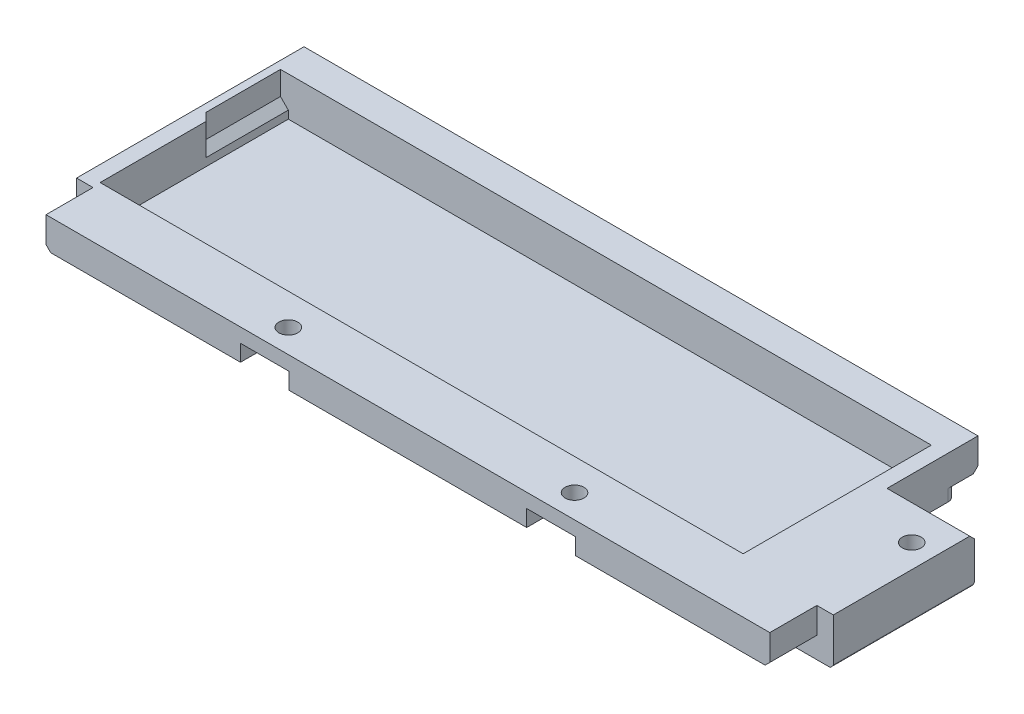
SolidWorks part; units mm, degrees
ref_plane "前视基准面" through (0, 0, 0) normal (0, 0, 1) x (1, 0, 0)
ref_plane "上视基准面" through (0, 0, 0) normal (0, 1, 0) x (1, 0, 0)
ref_plane "右视基准面" through (0, 0, 0) normal (1, 0, 0) x (0, 0, -1)
sketch "草图1" plane through (0, 0, 0) normal (0, 1, 0) x (1, 0, 0)
  line L1 (0, 0) -> (96.5, 0)
  line L2 (0, 0) -> (0, 35)
  line L3 (0, 35) -> (96.5, 35)
  line L4 (96.5, 0) -> (96.5, 35)
  dimension "D1" = 35
  dimension "D2" = 96.5
extrude "凸台-拉伸1" add sketch "草图1" along normal blind 6
sketch "草图2" plane through (0, 6, 0) normal (0, 1, 0) x (1, 0, 0)
  line L0 (96.5, 35) -> (0, 35) construction
  line L1 (2, 7) -> (84, 7)
  line L2 (2, 7) -> (2, 31)
  line L3 (2, 31) -> (84, 31)
  line L4 (84, 7) -> (84, 31)
  line L5 (0, 35) -> (0, 0) construction
  dimension "D1" = 24
  dimension "D2" = 82
  dimension "D3" = 4
  dimension "D4" = 2
extrude "切除-拉伸1" cut sketch "草图2" against normal blind 5
sketch "草图3" plane through (0, 0, 0) normal (0, 0, 1) x (1, 0, 0)
  line L0 (96.5, 6) -> (96.5, 0) construction
  line L1 (0, 0) -> (96.5, 0) construction
  line L2 (0, 6) -> (0, 0) construction
  line L3 (96.5, 6) -> (96.5, 0)
  line L4 (0, 0) -> (96.5, 0)
  line L5 (0, 6) -> (0, 0)
  line L6 (94.4, 6) -> (94.4, 2.1)
  line L7 (2.1, 2.1) -> (94.4, 2.1)
  line L8 (2.1, 6) -> (2.1, 2.1)
  line L9 (0, 6) -> (2.1, 6)
  line L10 (94.4, 6) -> (96.5, 6)
  dimension "D1" = 2.1
extrude "切除-拉伸2" cut sketch "草图3" against normal blind 6
sketch "草图4" plane through (0, 0, 0) normal (0, -1, 0) x (1, 0, 0)
  line L0 (0, -32.2) -> (86, -32.2) construction
  line L1 (86, -32.2) -> (86, -25) construction
  line L2 (87, -24) -> (96.5, -24) construction
  line L3 (0, -32.2) -> (85.95, -32.2)
  line L4 (86, -32.2) -> (86, -24) construction
  line L5 (86, -24) -> (96.5, -24)
  line L6 (86, -24) -> (85.95, -24)
  line L7 (85.95, -24) -> (85.95, -32.2)
  line L10 (96.5, -6) -> (0, -6)
  line L11 (0, -6) -> (0, -35)
  line L12 (0, -35) -> (96.5, -35)
  line L13 (96.5, -35) -> (96.5, -6)
  line L15 (0, -32.2) -> (0, -35)
  line L16 (0, -35) -> (96.5, -35)
  line L17 (96.5, -35) -> (96.5, -24)
  dimension "D2" = 0.1
  dimension "D1" = 0
extrude "切除-拉伸3" cut sketch "草图4" against normal blind 2.1
fillet "圆角1" radius 1 1 edges at (85.95, 1.05, -32.2)
chamfer "倒角1" distance 0.6 angle 45 4 edges at (42.475, 0, -32.2) (85.6571, 0, -31.9071) (85.95, 0, -27.6) (91.225, 0, -24)
chamfer "倒角2" distance 0.4 angle 45 2 edges at (0, 0, -18.8) (96.5, 0, -14.7)
fillet "圆角2" radius 0.2 4 edges at (0, 0.4, -19) (0.4, 0, -18.8) (96.1, 0, -14.7) (96.5, 0.4, -14.9)
sketch "草图5" plane through (0, 2.1, 0) normal (0, -1, 0) x (1, 0, 0)
  line L0 (85.95, -24) -> (85.95, -31.2) construction
  line L1 (96.5, -35) -> (85.95, -35)
  line L2 (96.5, -35) -> (96.5, -24)
  line L3 (96.5, -24) -> (85.95, -24)
  line L4 (85.95, -35) -> (85.95, -24)
  line L5 (96.5, -24) -> (85.95, -24) construction
extrude "切除-拉伸5" cut sketch "草图5" against normal through all
chamfer "倒角3" distance 0.6 angle 45 3 edges at (2.1, 2.1, -3) (94.4, 2.1, -3) (91.225, 6, -24)
chamfer "倒角4" distance 0.6 angle 45 1 edges at (42.975, 2.1, -35)
sketch "草图6" plane through (0, 6, 0) normal (0, 1, 0) x (1, 0, 0)
  line L1 (2, 31) -> (1, 31)
  line L2 (2, 31) -> (2, 21.5)
  line L3 (2, 21.5) -> (1, 21.5)
  line L4 (1, 31) -> (1, 21.5)
  dimension "D1" = 9.5
  dimension "D2" = 1
extrude "切除-拉伸6" cut sketch "草图6" against normal blind 3
chamfer "倒角5" distance 1 angle 45 1 edges at (2, 3, -26.25)
chamfer "倒角6" distance 1 angle 45 1 edges at (2, 4, -21.5)
sketch "草图7" plane through (0, 0, 0) normal (0, 0, 1) x (1, 0, 0)
  line L0 (69.5, 2) -> (69.5, 4) construction
  line L1 (63.5, 4) -> (63.5, 2) construction
  line L2 (33, 2) -> (33, 4) construction
  line L3 (27, 4) -> (27, 2) construction
  line L4 (69.5, 2) -> (69.5, 4) construction
  line L5 (63.5, 4) -> (63.5, 2) construction
  line L6 (33, 2) -> (33, 4) construction
  line L7 (27, 4) -> (27, 2) construction
  line L8 (27, 4) -> (33, 4) construction
  line L9 (63.5, 4) -> (69.5, 4) construction
  line L10 (93.8, 2.1) -> (2.7, 2.1) construction
  line L11 (69.6, 2.1) -> (63.4, 2.1)
  line L12 (26.9, 2.1) -> (26.9, 4.2)
  line L13 (26.9, 4.2) -> (33.1, 4.2)
  line L14 (33.1, 4.2) -> (33.1, 2.1)
  line L15 (63.4, 2.1) -> (63.4, 4.2)
  line L16 (63.4, 4.2) -> (69.6, 4.2)
  line L17 (69.6, 4.2) -> (69.6, 2.1)
  line L18 (33.1, 2.1) -> (26.9, 2.1)
  dimension "D1" = 0.1
  dimension "D2" = 0.1
  dimension "D3" = 0.2
  dimension "D4" = 0.1
extrude "切除-拉伸7" cut sketch "草图7" against normal blind 6
sketch "草图8" plane through (0, 4.2, 0) normal (0, -1, 0) x (1, 0, 0)
  circle A0 centre (66.5, -3) radius 1.2 construction
  circle A1 centre (30, -3) radius 1.2 construction
  circle A2 centre (66.5, -3) radius 1.2
  circle A3 centre (30, -3) radius 1.2
extrude "切除-拉伸8" cut sketch "草图8" against normal through all
ref_plane "基准面1" through (71.649, 13.84, -6.45) normal (0, 0, 1) x (1, 0, 0)
ref_plane "基准面2" through (59.6, 9.54, -28.6) normal (0, 0, 1) x (1, 0, 0)
sketch "草图11" plane through (0, 0, 0) normal (0, -1, 0) x (1, 0, 0)
  circle A0 centre (93.5, -19) radius 1.5 construction
  circle A1 centre (93.5, -19) radius 1.5 construction
  circle A2 centre (93.5, -19) radius 1.2
  circle A3 centre (93.5, -19) radius 2.05
  dimension "D1" = 2.4
  dimension "D2" = 4.1
extrude "切除-拉伸9" cut sketch "草图11" against normal through all contours A2
extrude "切除-拉伸10" cut sketch "草图11<3>" against normal blind 2 contours A3
sketch "草图11<3>" plane through (0, 0, 0) normal (0, -1, 0) x (1, 0, 0) same geometry as "草图11"
